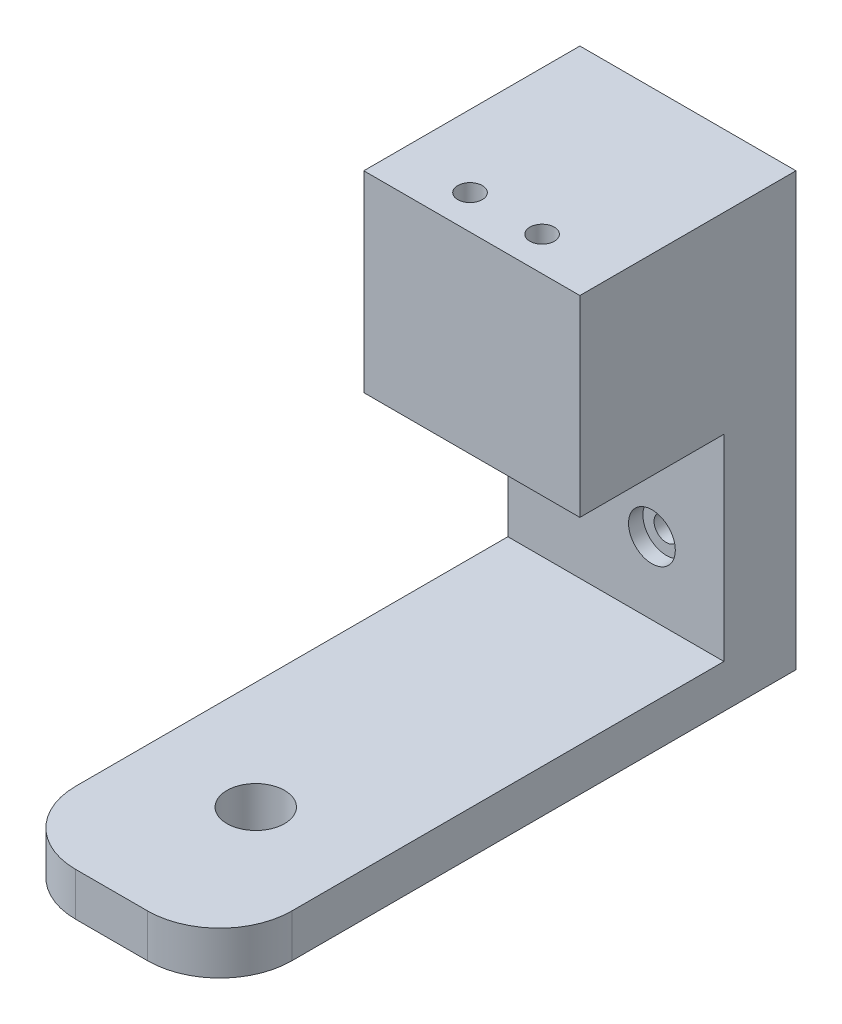
SolidWorks part; units mm, degrees
ref_plane "Plan de face" through (0, 0, 0) normal (0, 0, 1) x (1, 0, 0)
ref_plane "Plan de dessus" through (0, 0, 0) normal (0, 1, 0) x (1, 0, 0)
ref_plane "Plan de droite" through (0, 0, 0) normal (1, 0, 0) x (0, 0, -1)
sketch "Esquisse1" plane through (0, 0, 0) normal (0, 0, 1) x (1, 0, 0)
  line L1 (0, 0) -> (30, 0)
  line L2 (0, 0) -> (0, 60)
  line L3 (0, 60) -> (30, 60)
  line L4 (30, 0) -> (30, 60)
  dimension "D1" = 30
  dimension "D2" = 60
extrude "Boss.-Extru.1" add sketch "Esquisse1" along normal blind 10
sketch "Esquisse2" plane through (0, 0, 10) normal (0, 0, 1) x (1, 0, 0)
  line L0 (30, 0) -> (30, 60) construction
  line L1 (0, 0) -> (30, 0) construction
  line L2 (0, 60) -> (0, 0) construction
  line L3 (30, 0) -> (30, 6)
  line L4 (0, 0) -> (30, 0)
  line L5 (0, 6) -> (0, 0)
  line L6 (0, 6) -> (30, 6)
  dimension "D1" = 6
extrude "Boss.-Extru.2" add sketch "Esquisse2" along normal blind 70
sketch "Esquisse3" plane through (0, 0, 0) normal (0, -1, 0) x (1, 0, 0)
  line L0 (0, 80) -> (0, 0) construction
  line L1 (0, 0) -> (30, 0) construction
  circle A0 centre (15, 60) radius 4
  dimension "D3" = 8
  dimension "D1" = 15
  dimension "D2" = 60
extrude "Enlèv. mat.-Extru.1" cut sketch "Esquisse3" against normal up to surface (6 mm away) up to face at (15, 6, 45)
sketch "Esquisse4" plane through (0, 0, 10) normal (0, 0, 1) x (1, 0, 0)
  line L0 (30, 6) -> (30, 60) construction
  line L1 (30, 33.32) -> (30, 60)
  line L2 (0, 60) -> (0, 6) construction
  line L3 (30, 60) -> (0, 60) construction
  line L4 (0, 60) -> (0, 33.32)
  line L5 (30, 60) -> (0, 60)
  line L6 (0, 33.32) -> (30, 33.32)
  dimension "D1" = 26.68
extrude "Boss.-Extru.3" add sketch "Esquisse4" along normal blind 20
sketch "Esquisse5" plane through (0, 33.32, 0) normal (0, -1, 0) x (1, 0, 0)
  line L0 (0, 30) -> (0, 10) construction
  line L2 (0, 30) -> (30, 30) construction
  circle A0 centre (10, 25.25) radius 2.2
  circle A1 centre (20, 25.25) radius 2.2
  dimension "D3" = 4.4
  dimension "D4" = 4.4
  dimension "D1" = 10
  dimension "D2" = 10
  dimension "D5" = 4.75
  dimension "D6" = 4.75
hole_wizard "Dégagement M31" positions "Esquisse8" profile "Esquisse7" hole size "M3" standard "ISO"
sketch "Esquisse8" plane through (0, 33.32, 0) normal (0, -1, 0) x (-1, 0, 0)
  point P0 (-10, -25.25)
  point P3 (-20, -25.25)
sketch "Esquisse7" plane through (10, 33.32, 25.25) normal (1, 0, 0) x (0, 0, -1)
  line L0 (0, 0) -> (0, 27.7015)
  line L1 (0, 27.7015) -> (1.7, 26.68)
  line L2 (1.7, 26.68) -> (1.7, 0)
  line L5 (1.7, 0) -> (0, 0)
  line L10 (0, 27.7015) -> (-1.7, 26.68) construction
  line L11 (0, -6.35) -> (0, 107.95) construction
  dimension "Diamètre du perçage" = 3.4
  dimension "Profondeur du perçage" = 26.68
  dimension "Angle de pointe" = 118
sketch "Esquisse9" plane through (0, 0, 10) normal (0, 0, 1) x (1, 0, 0)
  line L0 (0, 33.32) -> (0, 6) construction
  line L1 (30, 6) -> (30, 33.32) construction
  line L2 (30, 6) -> (0, 6) construction
  line L3 (0, 33.32) -> (30, 33.32) construction
  circle A1 centre (20, 16) radius 1.5
  circle A2 centre (10, 23.32) radius 1.5
  dimension "D2" = 3
  dimension "D4" = 3
  dimension "D1" = 10
  dimension "D3" = 10
  dimension "D5" = 10
  dimension "D6" = 10
hole_wizard "Chambrage pour tête cylindrique fendue M31" positions "Esquisse10" profile "Esquisse12" counterbore size "M3" standard "ISO"
sketch "Esquisse10" plane through (0, 0, 10) normal (0, 0, 1) x (1, 0, 0)
  point P0 (10, 23.32)
  point P3 (20, 16)
sketch "Esquisse12" plane through (10, 23.32, 10) normal (1, 0, 0) x (0, -1, 0)
  line L0 (0, 0) -> (0, 11.0215)
  line L1 (0, 11.0215) -> (1.7, 10)
  line L2 (1.7, 10) -> (1.7, 2)
  line L3 (1.7, 2) -> (3.25, 2)
  line L4 (3.25, 2) -> (3.25, 0)
  line L5 (3.25, 0) -> (0, 0)
  line L10 (0, 11.0215) -> (-1.7, 10) construction
  line L11 (0, -6.35) -> (0, 107.95) construction
  dimension "Diamètre du perçage" = 3.4
  dimension "Profondeur du perçage" = 10
  dimension "Diamètre du chambrage" = 6.5
  dimension "Profondeur du chambrage" = 2
  dimension "Angle de pointe" = 118
fillet "Congé1" radius 10 2 edges at (30, 3, 80) (0, 3, 80)
equation "\"D4@Esquisse5\"=\"D3@Esquisse5\""
equation "\"D6@Esquisse5\"=\"D5@Esquisse5\""
